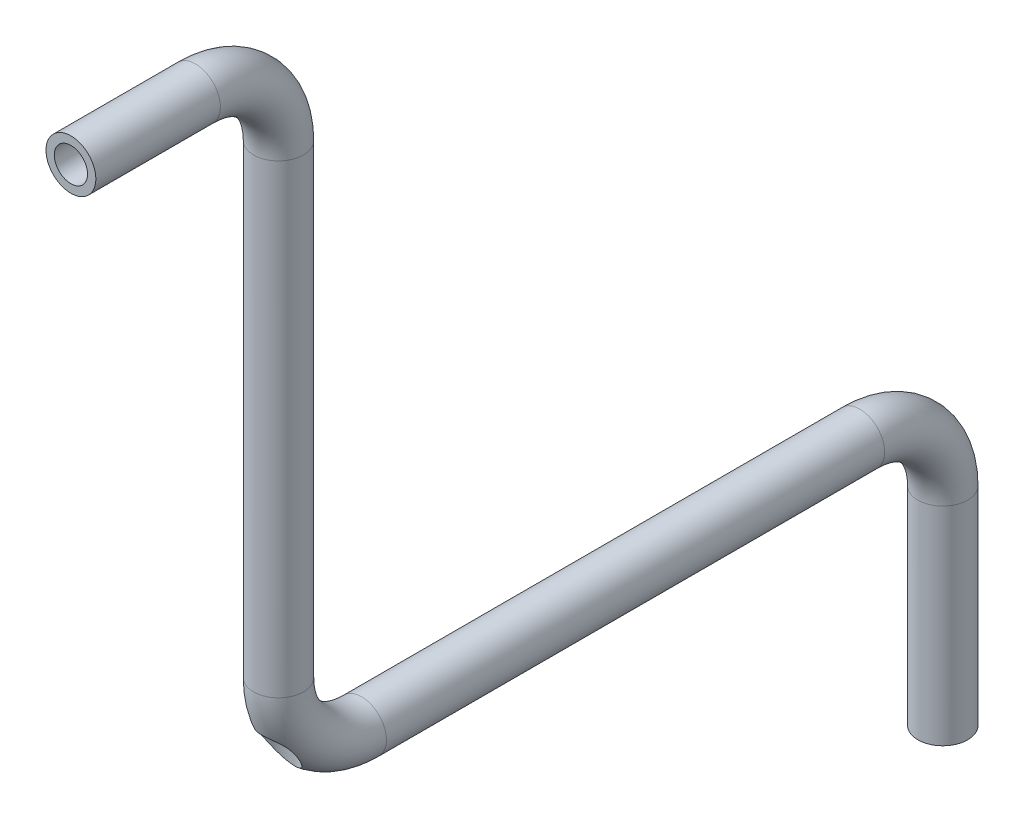
SolidWorks part; units mm, degrees
ref_plane "Front Plane" through (0, 0, 0) normal (0, 0, 1) x (1, 0, 0)
ref_plane "Top Plane" through (0, 0, 0) normal (0, 1, 0) x (1, 0, 0)
ref_plane "Right Plane" through (0, 0, 0) normal (1, 0, 0) x (0, 0, -1)
sketch "Sketch1" plane through (0, 0, 0) normal (1, 0, 0) x (0, 0, -1)
  line L0 (0, 660) -> (0, 100)
  line L1 (100, 0) -> (700, 0)
  line L2 (800, -100) -> (800, -350)
  line L3 (-100, 760) -> (-250, 760)
  arc A0 (0, 100) -> (100, 0) centre (100, 100) ccw
  arc A1 (0, 660) -> (-100, 760) centre (-100, 660) ccw
  arc A2 (700, 0) -> (800, -100) centre (700, -100) cw
  point P7 (0, 0)
  point P13 (800, 0)
  dimension "D4" = 100
  dimension "D1" = 100
  dimension "D5" = 100
  dimension "D2" = 800
  dimension "D3" = 350
sweep "Sweep-Thin2" add path "Sketch1" circular profile diameter 60 parameters "D1"=10, "D3"=60
sketch "Sketch25" plane through (0, 0, 0) normal (0, 1, 0) x (1, 0, 0)
  circle A0 centre (0, 0) radius 20
extrude "Cut-Extrude1" cut sketch "Sketch25" against normal blind 10 and the other way blind 86
